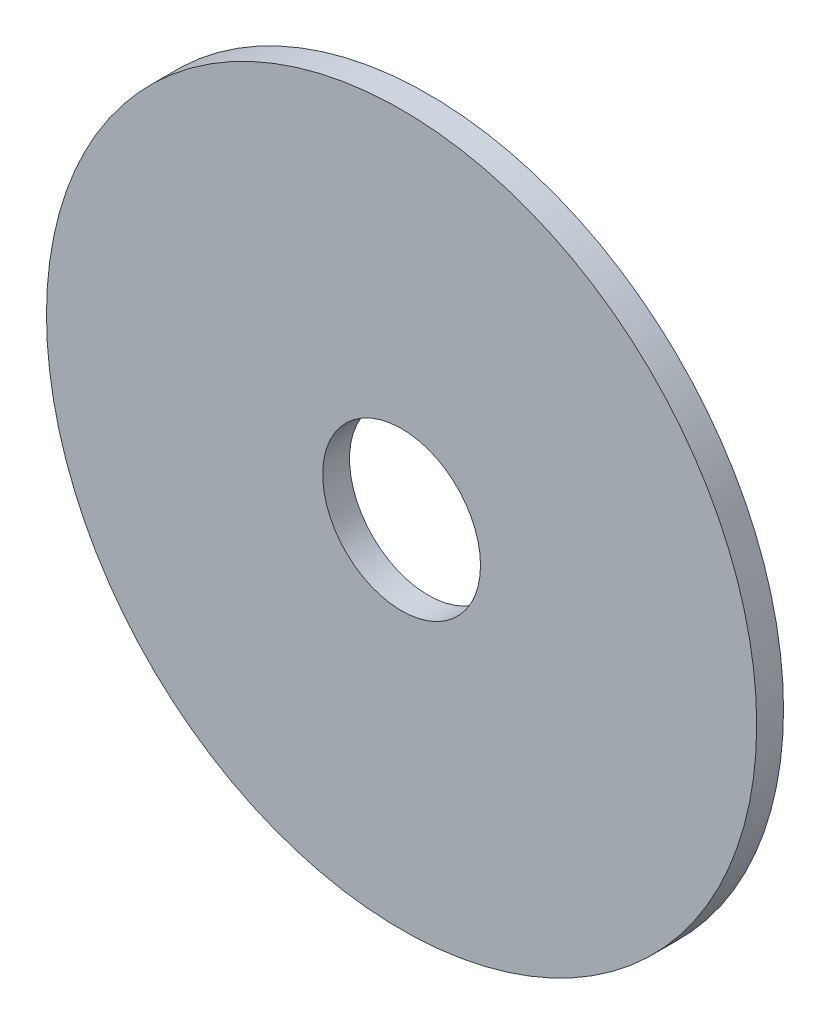
SolidWorks part; units mm, degrees
material "ABS PC"
ref_plane "Front Plane" through (0, 0, 0) normal (0, 0, 1) x (1, 0, 0)
ref_plane "Top Plane" through (0, 0, 0) normal (0, 1, 0) x (1, 0, 0)
ref_plane "Right Plane" through (0, 0, 0) normal (1, 0, 0) x (0, 0, -1)
sketch "Sketch1" plane through (0, 0, 0) normal (0, 0, 1) x (1, 0, 0)
  circle A0 centre (0, 0) radius 22.5
  circle A1 centre (0, 0) radius 5
  dimension "D1" = 45
  dimension "D2" = 10
extrude "Boss-Extrude1" add sketch "Sketch1" along normal blind 1.7
equation "\"smallPulleyTeeth\"= 15"
equation "\"largePulleyTeeth\"= 30"
equation "\"eighthThick\"= 2.9mm"
equation "\"sixteenthThick\" = 1.7mm"
equation "\"wheelEighthThick\"=3.0mm"
equation "\"quarterThick\"=5.9mm"
equation "\"bushingDiam\"= 7.85mm"
equation "\"plateBoltCircle\"= 65mm"
equation "\"plateBoltDiam\"= 5mm"
equation "\"D1@Boss-Extrude1\"=\"sixteenthThick\""
